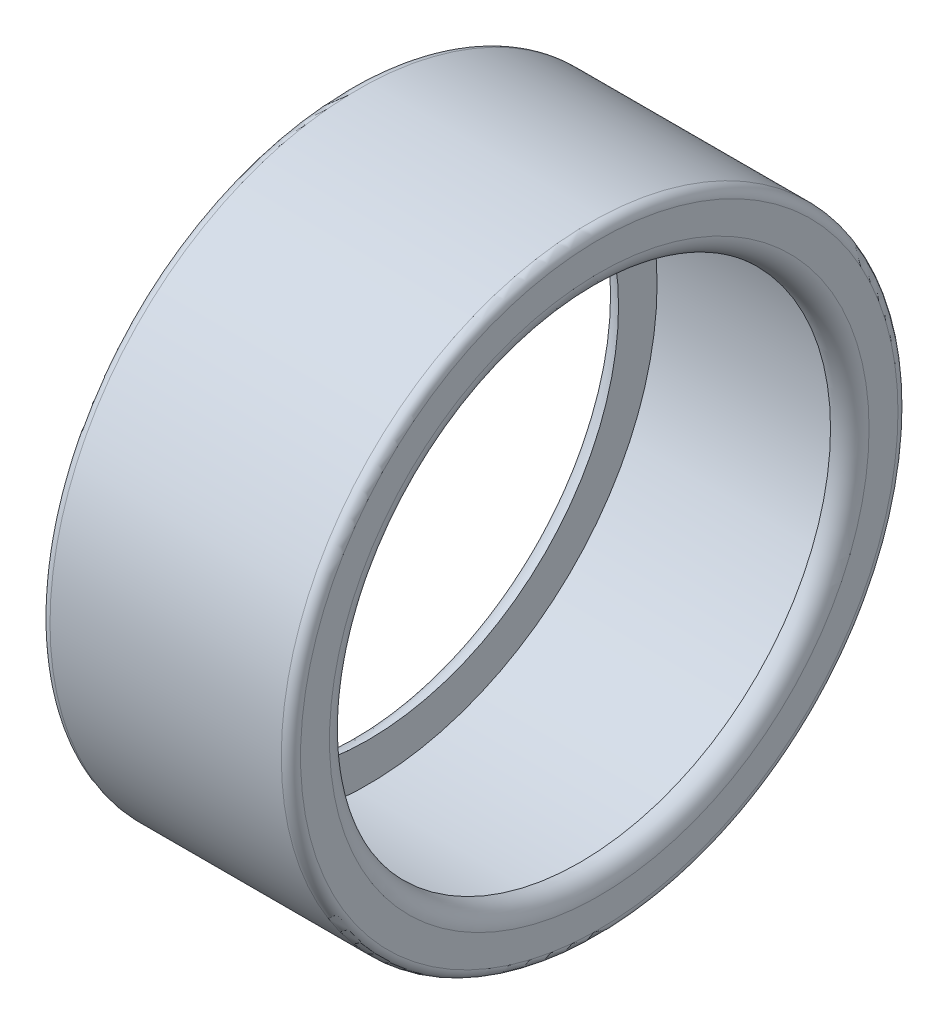
SolidWorks part; units mm, degrees
ref_plane "Front Plane" through (0, 0, 0) normal (0, 0, 1) x (1, 0, 0)
ref_plane "Top Plane" through (0, 0, 0) normal (0, 1, 0) x (1, 0, 0)
ref_plane "Right Plane" through (0, 0, 0) normal (1, 0, 0) x (0, 0, -1)
sketch "Sketch1" plane through (0, 0, 0) normal (1, 0, 0) x (0, 0, -1)
  circle A0 centre (0, 0) radius 26
  circle A1 centre (0, 0) radius 32
  dimension "D1" = 52
  dimension "D2" = 6
extrude "Boss-Extrude1" add sketch "Sketch1" along normal blind 26
fillet "Fillet1" radius 1 2 edges at (0, 0, -32) (26, 0, -32)
fillet "Fillet2" radius 2 2 edges at (26, 0, -26) (0, 0, -26)
shell "Shell1" thickness 2 removed face at (24, 0, -26)
